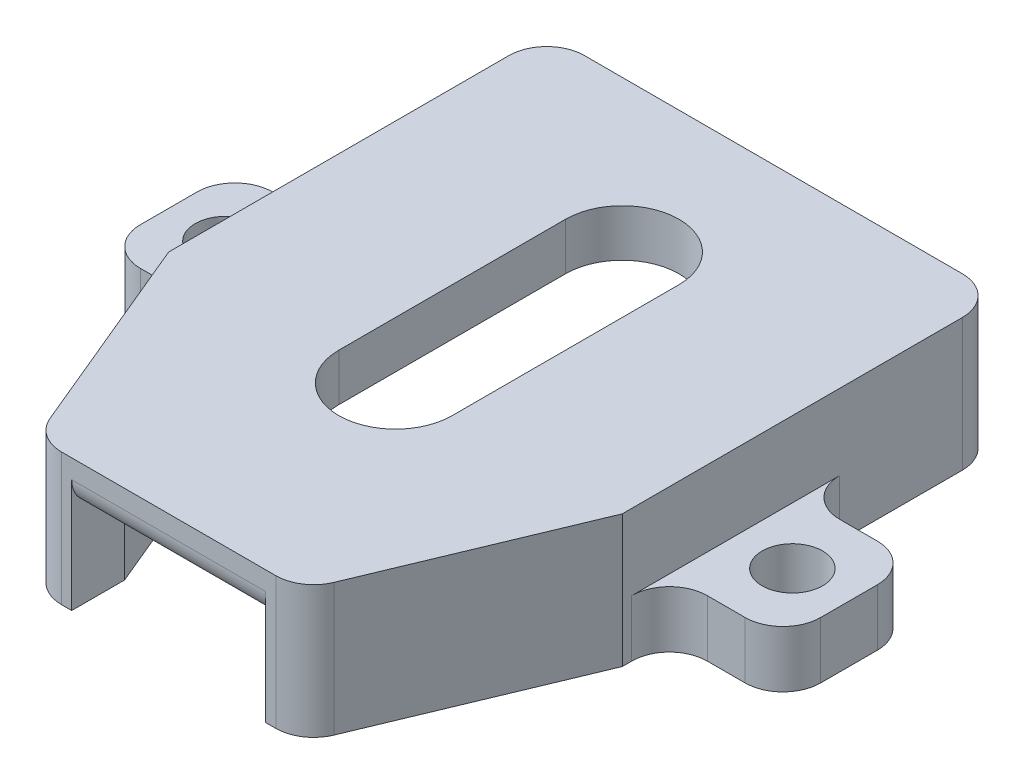
SolidWorks part; units mm, degrees
ref_plane "前视基准面" through (0, 0, 0) normal (0, 0, 1) x (1, 0, 0)
ref_plane "上视基准面" through (0, 0, 0) normal (0, 1, 0) x (1, 0, 0)
ref_plane "右视基准面" through (0, 0, 0) normal (1, 0, 0) x (0, 0, -1)
sketch "草图1" plane through (0, 0, 0) normal (0, 0, 1) x (1, 0, 0)
  line L0 (0, 148.5) -> (0, -94.9538) construction
  line L1 (105, -148.5) -> (-105, -148.5) construction
  line L2 (105, -148.5) -> (105, 148.5) construction
  line L3 (105, 148.5) -> (-105, 148.5) construction
  line L4 (-105, -148.5) -> (-105, 148.5) construction
  line L5 (105, -148.5) -> (-105, 148.5) construction
  line L6 (105, 148.5) -> (-105, -148.5) construction
  line L7 (35.8892, 121.6645) -> (-35.8892, 121.6645)
  line L8 (-35.8892, 121.6645) -> (-66.9017, 102.292)
  line L9 (-75, 40.9339) -> (-75, 31.2613)
  line L10 (-66.9017, 102.292) -> (-66.9017, 52.8701)
  line L11 (75, 40.9339) -> (75, 31.2613)
  line L12 (66.9017, 102.292) -> (66.9017, 52.8701)
  line L13 (35.8892, 121.6645) -> (66.9017, 102.292)
  line L14 (-75, 31.2613) -> (75, 31.2613)
  line L15 (-60, -148.5) -> (-60, -91.8129)
  line L16 (-75, 23.94) -> (75, 23.94)
  line L17 (-75, 23.94) -> (-75, 10.5626)
  line L18 (-38.8455, -105.5906) -> (-66.4608, -113.7617)
  line L19 (-66.4608, -113.7617) -> (-70.1743, -102.7328)
  line L20 (75, 23.94) -> (75, 10.5626)
  line L21 (66.4608, -113.7617) -> (70.1743, -102.7328)
  line L22 (38.8455, -105.5906) -> (66.4608, -113.7617)
  line L23 (-105, 93.0519) -> (105, 93.0519)
  line L24 (-105, 63.0519) -> (105, 63.0519)
  line L25 (-105, -90.0629) -> (-70.5337, -90.0629)
  line L26 (-105, -60.0629) -> (-67.4027, -60.0629)
  line L27 (60, -148.5) -> (60, 148.5)
  line L28 (-60, -58.3129) -> (-45, -58.3129)
  line L29 (-60, -61.8129) -> (-45, -61.8129)
  line L30 (-36, -58.3129) -> (-21, -58.3129)
  line L31 (-36, -61.8129) -> (-21, -61.8129)
  line L32 (-60, -88.3129) -> (-45, -88.3129)
  line L33 (-60, -91.8129) -> (-45, -91.8129)
  line L34 (-36, -88.3129) -> (-21, -88.3129)
  line L35 (-36, -91.8129) -> (-21, -91.8129)
  line L36 (-60, -58.3129) -> (-60, 148.5)
  line L37 (-19.25, -90.0629) -> (105, -90.0629)
  line L38 (-19.25, -60.0629) -> (19.25, -60.0629)
  line L39 (-60, -88.3129) -> (-60, -61.8129)
  line L40 (21, -58.3129) -> (36, -58.3129)
  line L41 (45, -58.3129) -> (60, -58.3129)
  line L42 (60, -61.8129) -> (45, -61.8129)
  line L43 (36, -61.8129) -> (21, -61.8129)
  line L44 (21, -88.3129) -> (36, -88.3129)
  line L45 (21, -91.8129) -> (36, -91.8129)
  line L46 (45, -88.3129) -> (60, -88.3129)
  line L47 (45, -91.8129) -> (60, -91.8129)
  line L48 (37.75, -60.0629) -> (43.25, -60.0629)
  line L49 (58.25, -60.0629) -> (105, -60.0629)
  line L50 (-60, 94.8019) -> (-45, 94.8019)
  line L51 (-36, 94.8019) -> (-21, 94.8019)
  line L52 (-60, 91.3019) -> (-45, 91.3019)
  line L53 (-36, 91.3019) -> (-21, 91.3019)
  line L54 (-60, 64.8019) -> (-45, 64.8019)
  line L55 (-60, 61.3019) -> (-45, 61.3019)
  line L56 (-36, 64.8019) -> (-21, 64.8019)
  line L57 (-36, 61.3019) -> (-21, 61.3019)
  line L58 (21, 94.8019) -> (36, 94.8019)
  line L59 (21, 91.3019) -> (36, 91.3019)
  line L60 (45, 94.8019) -> (60, 94.8019)
  line L61 (45, 91.3019) -> (60, 91.3019)
  line L62 (21, 61.3019) -> (36, 61.3019)
  line L63 (21, 64.8019) -> (36, 64.8019)
  line L64 (45, 61.3019) -> (60, 61.3019)
  line L65 (45, 64.8019) -> (60, 64.8019)
  line L66 (-33.1709, -104.7687) -> (33.1709, -104.7687)
  line L67 (0, -104.7687) -> (0, -148.5) construction
  arc A0 (-75, 40.9339) -> (-66.9017, 52.8701) centre (-79.7474, 52.8701) ccw
  arc A1 (75, 40.9339) -> (66.9017, 52.8701) centre (79.7474, 52.8701) cw
  arc A3 (-60, -88.3129) -> (-60, -91.8129) centre (-60, -90.0629) ccw
  arc A4 (-60, -58.3129) -> (-60, -61.8129) centre (-60, -60.0629) ccw
  circle A5 centre (-60, 63.0519) radius 1.75
  circle A6 centre (-60, 93.0519) radius 1.75
  circle A7 centre (60, 93.0519) radius 1.75
  circle A8 centre (60, 63.0519) radius 1.75
  arc A9 (60, -91.8129) -> (60, -88.3129) centre (60, -90.0629) ccw
  arc A10 (60, -61.8129) -> (60, -58.3129) centre (60, -60.0629) ccw
  arc A11 (-36, -58.3129) -> (-36, -61.8129) centre (-36, -60.0629) ccw
  arc A12 (-36, -88.3129) -> (-36, -91.8129) centre (-36, -90.0629) ccw
  arc A13 (36, -61.8129) -> (36, -58.3129) centre (36, -60.0629) ccw
  arc A14 (36, -91.8129) -> (36, -88.3129) centre (36, -90.0629) ccw
  arc A15 (-45, -61.8129) -> (-45, -58.3129) centre (-45, -60.0629) ccw
  arc A16 (-21, -61.8129) -> (-21, -58.3129) centre (-21, -60.0629) ccw
  arc A17 (-45, -91.8129) -> (-45, -88.3129) centre (-45, -90.0629) ccw
  arc A18 (-21, -91.8129) -> (-21, -88.3129) centre (-21, -90.0629) ccw
  arc A19 (45, -58.3129) -> (45, -61.8129) centre (45, -60.0629) ccw
  arc A20 (21, -58.3129) -> (21, -61.8129) centre (21, -60.0629) ccw
  arc A21 (21, -88.3129) -> (21, -91.8129) centre (21, -90.0629) ccw
  arc A22 (45, -88.3129) -> (45, -91.8129) centre (45, -90.0629) ccw
  circle A23 centre (-36, 93.0519) radius 1.75
  circle A24 centre (-36, 63.0519) radius 1.75
  circle A25 centre (36, 93.0519) radius 1.75
  circle A26 centre (36, 63.0519) radius 1.75
  circle A27 centre (-45, 93.0519) radius 1.75
  circle A28 centre (-21, 93.0519) radius 1.75
  circle A29 centre (-45, 63.0519) radius 1.75
  circle A30 centre (-21, 63.0519) radius 1.75
  circle A31 centre (21, 93.0519) radius 1.75
  circle A32 centre (21, 63.0519) radius 1.75
  circle A33 centre (45, 93.0519) radius 1.75
  circle A34 centre (45, 63.0519) radius 1.75
  arc A35 (33.1709, -104.7687) -> (38.8455, -105.5906) centre (33.1709, -124.7687) cw
  arc A36 (-33.1709, -104.7687) -> (-38.8455, -105.5906) centre (-33.1709, -124.7687) ccw
  spline S0 degree 3 poles (-75, 10.5626) (-72.6959, 1.9073) (-70.3396, -13.3728) (-67.1028, -43.6255) (-66.7657, -72.9327) (-71.8903, -95.1489) (-70.1743, -102.7328) knots 0 0 0 0 0.235247 0.406294 0.801186 1 1 1 1
  spline S1 degree 3 poles (75, 10.5626) (72.6959, 1.9073) (70.3396, -13.3728) (67.1028, -43.6255) (66.7657, -72.9327) (71.8903, -95.1489) (70.1743, -102.7328) knots 0 0 0 0 0.235247 0.406294 0.801186 1 1 1 1
  point P0 (0, 0)
  point P27 (0, 121.6645)
  point P42 (0, -94.0966)
  dimension "D1" = 60
  dimension "D4" = 20
  dimension "D5" = 24
  dimension "D7" = 24
  dimension "D9" = 15
  dimension "D10" = 15
  dimension "D13" = 24
  dimension "D17" = 15
  dimension "D2" = 30
  dimension "D3" = 30
  dimension "D6" = 24
  dimension "D8" = 24
  dimension "D11" = 15
  dimension "D12" = 15
  dimension "D14" = 24
  dimension "D15" = 24
  dimension "D16" = 24
  dimension "D18" = 15
  dimension "D19" = 15
  dimension "D20" = 15
  dimension "D21" = 15
  dimension "D22" = 15
  dimension "D23" = 15
  dimension "D24" = 15
  dimension "D25" = 15
  dimension "D26" = 15
  dimension "D27" = 15
  dimension "D28" = 15
  dimension "D29" = 3.5
  dimension "D30" = 3.5
  dimension "D31" = 3.5
extrude "凸台-拉伸1" add sketch "草图1" along normal blind 3 contours A34 L24 A26 L62 A32 A30 L57 A24 A29 L55 L36 L14 L27 L64 | A5 L24 L10 A0 L9 L14 L36 | A6 L23 L10 L24 A5 L36 | A6 L36 L8 L10 L23 | A33 L60 L27 L13 L7 L8 L36 L50 A27 L23 A23 L51 A28 A31 L58 A25 | A34 L65 L27 L61 A33 L23 A25 L59 A31 A28 L53 A23 A27 L52 L36 L54 A29 L24 A24 L56 A30 A32 L63 A26 | A7 L23 L12 L13 L27 | A8 L24 L12 L23 A7 L27 | A8 L27 L14 L11 A1 L12 L24 | A22 L46 L27 L42 A19 A13 L43 A20 A16 L31 A11 L30 L40 L41 L16 L36 L28 A15 L29 L39 L32 A17 L33 L15 L18 L22 L47 A14 L45 A21 A18 L35 A12 L34 | L17 S0 L19 L18 L15 A3 L39 A4 L36 L16 | S1 L20 L16 L27 A10 L49 | S1 L49 A10 L27 A9 L37 | S1 L37 A9 L27 L22 L21 region at (0, 106.7597, 0) region at (63.3118, 98.9762, 0) region at (-63.3118, 98.9762, 0) region at (63.5153, 78.0519, 0) region at (-63.5153, 78.0519, 0) region at (65.7633, 44.067, 0) region at (0, 78.0519, 0) region at (-65.7633, 44.067, 0) region at (0, 46.6707, 0) region at (0, -40.0712, 0) region at (65.6849, -11.6712, 0) region at (-65.3451, -38.0027, 0) region at (64.4303, -76.0355, 0) region at (65.0264, -100.7629, 0)
sketch "草图7" plane through (0, 0, 0) normal (0, 0, -1) x (-1, 0, 0)
  line L0 (0, 121.6645) -> (0, -104.7687) construction
  line L1 (-35.8892, 121.6645) -> (35.8892, 121.6645) construction
  line L2 (33.1709, -104.7687) -> (-33.1709, -104.7687) construction
  line L3 (0, 41.2613) -> (-21, 41.2613) construction
  line L4 (0, 41.2613) -> (21, 41.2613) construction
  line L5 (0, 13.94) -> (-21, 13.94) construction
  line L6 (0, 13.94) -> (21, 13.94) construction
  line L7 (75, 23.94) -> (-75, 23.94) construction
  line L8 (75, 31.2613) -> (-75, 31.2613) construction
  circle A0 centre (-21, 41.2613) radius 1.75
  circle A1 centre (21, 41.2613) radius 1.75
  circle A2 centre (-21, 13.94) radius 2.25
  circle A3 centre (21, 13.94) radius 2.25
  dimension "D1" = 10
  dimension "D2" = 10
extrude "切除-拉伸2" cut sketch "草图7" against normal through all
sketch "草图9" plane through (0, 0, 3) normal (0, 0, 1) x (1, 0, 0)
  line L0 (-70.7828, -98.747) -> (70.7828, -98.747) construction
  line L1 (0, -98.747) -> (0, -104.7687) construction
  line L2 (55, -100.497) -> (20, -100.497)
  line L3 (-55, -96.997) -> (-20, -96.997)
  line L4 (-55, -100.497) -> (-20, -100.497)
  line L5 (-33.1709, -104.7687) -> (33.1709, -104.7687) construction
  line L6 (55, -96.997) -> (20, -96.997)
  arc A0 (-55, -96.997) -> (-55, -100.497) centre (-55, -98.747) ccw
  arc A1 (-20, -100.497) -> (-20, -96.997) centre (-20, -98.747) ccw
  arc A2 (20, -100.497) -> (20, -96.997) centre (20, -98.747) cw
  arc A3 (55, -96.997) -> (55, -100.497) centre (55, -98.747) cw
  spline S0 degree 3 poles (-75, 10.5626) (-72.6959, 1.9073) (-70.3396, -13.3728) (-67.1028, -43.6255) (-66.7657, -72.9327) (-71.8903, -95.1489) (-70.1743, -102.7328) knots 0 0 0 0 0.235247 0.406294 0.801186 1 1 1 1 construction
  spline S1 degree 3 poles (75, 10.5626) (72.6959, 1.9073) (70.3396, -13.3728) (67.1028, -43.6255) (66.7657, -72.9327) (71.8903, -95.1489) (70.1743, -102.7328) knots 0 0 0 0 0.235247 0.406294 0.801186 1 1 1 1 construction
  dimension "D1" = 35
  dimension "D2" = 20
extrude "切除-拉伸4" cut sketch "草图9" against normal blind 3
sketch "草图10" plane through (0, 0, 3) normal (0, 0, 1) x (1, 0, 0)
  line L0 (-21, -60.0629) -> (-21, -90.0629) construction
  line L1 (21, -60.0629) -> (21, -90.0629) construction
  line L2 (-21, -75.0629) -> (-17.5, -75.0629) construction
  line L4 (12.5, -80.0629) -> (-12.5, -80.0629)
  line L6 (12.5, -70.0629) -> (-12.5, -70.0629)
  line L11 (17.5, -75.0629) -> (21, -75.0629) construction
  arc A0 (-12.5, -70.0629) -> (-12.5, -80.0629) centre (-12.5, -75.0629) ccw
  arc A1 (12.5, -80.0629) -> (12.5, -70.0629) centre (12.5, -75.0629) ccw
  point P11 (0, -75.0629)
extrude "切除-拉伸5" cut sketch "草图10" against normal blind 3
sketch "草图11" plane through (0, 0, 3) normal (0, 0, 1) x (1, 0, 0)
  line L0 (-21, 93.0519) -> (-21, 63.0519) construction
  line L1 (21, 93.0519) -> (21, 63.0519) construction
  line L2 (-21, 78.0519) -> (-20, 78.0519) construction
  line L4 (15, 73.0519) -> (-15, 73.0519)
  line L6 (15, 83.0519) -> (-15, 83.0519)
  line L10 (20, 78.0519) -> (21, 78.0519) construction
  arc A0 (-15, 83.0519) -> (-15, 73.0519) centre (-15, 78.0519) ccw
  arc A1 (15, 73.0519) -> (15, 83.0519) centre (15, 78.0519) ccw
  point P10 (0, 78.0519)
  dimension "D1" = 30
extrude "切除-拉伸8" cut sketch "草图11" against normal blind 3
sketch "草图12" plane through (0, 0, 3) normal (0, 0, 1) x (1, 0, 0)
  line L0 (0, 121.6645) -> (0, 83.0519) construction
  line L1 (35.8892, 121.6645) -> (-35.8892, 121.6645) construction
  line L2 (15, 83.0519) -> (-15, 83.0519) construction
  circle A0 centre (0, 106.3718) radius 11 construction
  circle A1 centre (0, 106.3718) radius 8 construction
  circle A2 centre (0, 114.3718) radius 1.7
  circle A3 centre (0, 98.3718) radius 1.7
  circle A4 centre (8, 106.3718) radius 1.7
  circle A5 centre (-8, 106.3718) radius 1.7
extrude "切除-拉伸9" cut sketch "草图12" against normal blind 3
sketch "草图13" plane through (0, 0, 3) normal (0, 0, 1) x (1, 0, 0)
  line L0 (0, -104.7687) -> (0, -80.0629) construction
  line L1 (-33.1709, -104.7687) -> (33.1709, -104.7687) construction
  line L2 (-12.5, -80.0629) -> (12.5, -80.0629) construction
  circle A0 centre (0, -92.4158) radius 8 construction
  circle A1 centre (0, -84.4158) radius 1.7
  circle A2 centre (8, -92.4158) radius 1.7
  circle A3 centre (0, -100.4158) radius 1.7
  circle A4 centre (-8, -92.4158) radius 1.7
extrude "切除-拉伸11" cut sketch "草图13" against normal blind 3
sketch "草图14" plane through (0, 0, 3) normal (0, 0, 1) x (1, 0, 0)
  line L0 (0, 23.94) -> (0, -104.7687) construction
  line L1 (-55.4755, 8.9197) -> (-55.4755, -46.0803)
  line L2 (-58.9755, 8.9197) -> (-58.9755, -46.0803)
  line L3 (-75, 23.94) -> (75, 23.94) construction
  line L4 (-33.1709, -104.7687) -> (33.1709, -104.7687) construction
  line L5 (58.9755, 8.9197) -> (58.9755, -46.0803)
  line L6 (55.4755, 8.9197) -> (55.4755, -46.0803)
  arc A0 (-55.4755, 8.9197) -> (-58.9755, 8.9197) centre (-57.2255, 8.9197) ccw
  arc A1 (-58.9755, -46.0803) -> (-55.4755, -46.0803) centre (-57.2255, -46.0803) ccw
  arc A2 (58.9755, -46.0803) -> (55.4755, -46.0803) centre (57.2255, -46.0803) cw
  arc A3 (55.4755, 8.9197) -> (58.9755, 8.9197) centre (57.2255, 8.9197) cw
extrude "切除-拉伸12" cut sketch "草图14" against normal through all
fillet "圆角1" radius 2 2 edges at (75, 31.2613, 1.5) (-75, 31.2613, 1.5)
fillet "圆角2" radius 2 2 edges at (-75, 23.94, 1.5) (75, 23.94, 1.5)
sketch "草图15" plane through (0, 0, 0) normal (0, 0, -1) x (-1, 0, 0)
  line L0 (0, 121.6645) -> (0, 31.2613) construction
  line L1 (-35.8892, 121.6645) -> (35.8892, 121.6645) construction
  line L2 (73, 31.2613) -> (-73, 31.2613) construction
  line L3 (-27.5188, 121.6645) -> (-63.6963, 99.0657) construction
  line L4 (-35.8892, 121.6645) -> (-66.9017, 102.292) construction
  line L5 (-61.1842, 102.4035) -> (-34.7748, 118.9006)
  line L6 (-59.5948, 99.8591) -> (-33.1854, 116.3562)
  line L7 (27.5188, 121.6645) -> (63.6963, 99.0657) construction
  line L8 (59.5948, 99.8591) -> (33.1854, 116.3562)
  line L9 (61.1842, 102.4035) -> (34.7748, 118.9006)
  arc A0 (-61.1842, 102.4035) -> (-59.5948, 99.8591) centre (-60.3895, 101.1313) ccw
  arc A1 (-33.1854, 116.3562) -> (-34.7748, 118.9006) centre (-33.9801, 117.6284) ccw
  arc A2 (33.1854, 116.3562) -> (34.7748, 118.9006) centre (33.9801, 117.6284) cw
  arc A3 (61.1842, 102.4035) -> (59.5948, 99.8591) centre (60.3895, 101.1313) cw
extrude "切除-拉伸13" cut sketch "草图15" against normal through all
sketch "草图16" plane through (0, 0, 0) normal (0, 0, -1) x (-1, 0, 0)
  line L0 (0, 121.6645) -> (0, 31.2613) construction
  line L1 (-35.8892, 121.6645) -> (35.8892, 121.6645) construction
  line L2 (73, 31.2613) -> (-73, 31.2613) construction
  line L3 (-21, 41.2613) -> (-66.71, 41.2613) construction
  line L4 (-62, 43.0113) -> (-32, 43.0113)
  line L5 (-62, 39.5113) -> (-32, 39.5113)
  line L6 (21, 41.2613) -> (66.71, 41.2613) construction
  line L7 (62, 39.5113) -> (32, 39.5113)
  line L8 (62, 43.0113) -> (32, 43.0113)
  line L9 (-75, 40.9339) -> (-75, 33.2613) construction
  arc A0 (-62, 43.0113) -> (-62, 39.5113) centre (-62, 41.2613) ccw
  arc A1 (-32, 39.5113) -> (-32, 43.0113) centre (-32, 41.2613) ccw
  arc A2 (32, 39.5113) -> (32, 43.0113) centre (32, 41.2613) cw
  arc A3 (62, 43.0113) -> (62, 39.5113) centre (62, 41.2613) cw
  dimension "D2" = 13
sketch "草图17" plane through (0, 0, 0) normal (0, 0, -1) x (-1, 0, 0)
  text T0 "Y" font "黑体" height in points 72
extrude "切除-拉伸15" cut sketch "草图17" against normal through all
sketch "草图18" plane through (0, 0, 0) normal (0, 0, -1) x (-1, 0, 0)
  text T0 "H" font "黑体" height in points 72
extrude "切除-拉伸16" cut sketch "草图18" against normal through all
sketch "草图20" plane through (0, 0, 0) normal (0, 0, -1) x (-1, 0, 0)
  line L0 (-66.9017, 102.292) -> (-66.9017, 52.8701) construction
  line L1 (-66.9017, 95.8596) -> (66.9017, 95.8596)
  line L2 (-66.9017, 95.8596) -> (-66.9017, 52.8701)
  line L3 (-66.9017, 52.8701) -> (66.9017, 52.8701)
  line L4 (66.9017, 95.8596) -> (66.9017, 52.8701)
extrude "凸台-拉伸2" add sketch "草图20" against normal blind 3
sketch "草图21" plane through (0, 0, 0) normal (0, 0, -1) x (-1, 0, 0)
  line L1 (-64.7663, -56.4228) -> (64.4409, -56.4228)
  line L2 (-64.7663, -56.4228) -> (-64.7663, -95.2117)
  line L3 (-64.7663, -95.2117) -> (64.4409, -95.2117)
  line L4 (64.4409, -56.4228) -> (64.4409, -95.2117)
extrude "凸台-拉伸3" add sketch "草图21" against normal blind 3
sketch "草图22" plane through (0, 0, 0) normal (0, 0, -1) x (-1, 0, 0)
  line L1 (-46.7188, -3.1128) -> (-25.8503, -3.1128)
  line L2 (-46.7188, -3.1128) -> (-46.7188, -34.3233)
  line L3 (-46.7188, -34.3233) -> (-25.8503, -34.3233)
  line L4 (-25.8503, -3.1128) -> (-25.8503, -34.3233)
  line L5 (28.8143, -3.1128) -> (49.8675, -3.1128)
  line L6 (28.8143, -3.1128) -> (28.8143, -33.2152)
  line L7 (28.8143, -33.2152) -> (49.8675, -33.2152)
  line L8 (49.8675, -3.1128) -> (49.8675, -33.2152)
extrude "凸台-拉伸4" add sketch "草图22" against normal blind 3
sketch "草图24" plane through (0, 0, 0) normal (0, 0, -1) x (-1, 0, 0)
  line L1 (-64.9961, 44.3276) -> (-28.6954, 44.3276)
  line L2 (-64.9961, 44.3276) -> (-64.9961, 38.3743)
  line L3 (-64.9961, 38.3743) -> (-28.6954, 38.3743)
  line L4 (-28.6954, 44.3276) -> (-28.6954, 38.3743)
  line L5 (29.2405, 44.3276) -> (65.8315, 44.3276)
  line L6 (29.2405, 44.3276) -> (29.2405, 38.3743)
  line L7 (29.2405, 38.3743) -> (65.8315, 38.3743)
  line L8 (65.8315, 44.3276) -> (65.8315, 38.3743)
extrude "凸台-拉伸5" add sketch "草图24" against normal blind 3
sketch "草图25" plane through (0, 0, 0) normal (0, 0, -1) x (-1, 0, 0)
  line L0 (-32.6582, 113.0113) -> (-14.6582, 113.0113)
  line L1 (-32.6582, 109.5113) -> (-14.6582, 109.5113)
  line L2 (-21, 41.2613) -> (21, 41.2613)
  line L3 (-0.3165, 111.2613) -> (0, 41.2613) construction
  line L4 (14.3418, 113.0113) -> (32.3418, 113.0113)
  line L5 (32.3418, 41.2613) -> (-32.6582, 41.2613)
  line L6 (32.3418, 41.2613) -> (32.3418, 111.2613)
  line L8 (-32.6582, 41.2613) -> (-32.6582, 111.2613)
  line L9 (32.3418, 41.2613) -> (-32.6582, 111.2613) construction
  line L10 (30.7168, 109.5113) -> (-32.6582, 41.2613) construction
  line L11 (14.3418, 109.5113) -> (32.3418, 109.5113)
  line L12 (32.3418, 76.2613) -> (-32.6582, 76.2613) construction
  line L13 (12.5918, 111.2613) -> (-12.9082, 111.2613)
  line L14 (12.5918, 41.2613) -> (-12.9082, 41.2613)
  line L15 (14.3418, 43.0113) -> (32.3418, 43.0113)
  line L16 (14.3418, 39.5113) -> (32.3418, 39.5113)
  line L17 (-32.6582, 43.0113) -> (-14.6582, 43.0113)
  line L18 (-32.6582, 39.5113) -> (-14.6582, 39.5113)
  circle A0 centre (-32.6582, 111.2613) radius 1.75
  arc A1 (32.3418, 109.5113) -> (32.3418, 113.0113) centre (32.3418, 111.2613) ccw
  arc A2 (-14.6582, 109.5113) -> (-14.6582, 113.0113) centre (-14.6582, 111.2613) ccw
  arc A3 (14.3418, 113.0113) -> (14.3418, 109.5113) centre (14.3418, 111.2613) ccw
  arc A4 (14.3418, 39.5113) -> (14.3418, 43.0113) centre (14.3418, 41.2613) cw
  arc A5 (-14.6582, 43.0113) -> (-14.6582, 39.5113) centre (-14.6582, 41.2613) cw
  arc A6 (32.3418, 43.0113) -> (32.3418, 39.5113) centre (32.3418, 41.2613) cw
  circle A7 centre (-32.6582, 41.2613) radius 1.75
  point P9 (-0.1582, 76.2613)
  circle M6 centre (-21, 41.2613) radius 1.75
  circle M7 centre (21, 41.2613) radius 1.75
  dimension "D1" = 18
  dimension "D2" = 18
extrude "切除-拉伸17" cut sketch "草图25" against normal through all contours A0 | A2 L0 A0 L1 | L4 A3 L11 A1 | A7 L8 L5 | A7 L5 L8 | L17 A7 L5 M6 | L5 A7 L18 M6 | A5 L17 L2 M6 | A5 L2 L18 M6 | L17 L5 L2 M6 | L18 L2 L5 M6 | A4 L2 L15 M7 | A4 L16 L2 M7 | L16 L5 L2 M7 | L15 L2 L5 M7 | L15 L5 L6 M7 | A6 L6 L5 L16 M7 region at (22.2838, 111.2613, 0) region at (31.4558, 112.4638, 0) region at (31.9155, 42.0041, 0) region at (26.8291, 42.1772, 0) region at (32.9058, 41.0138, 0) region at (-23.3418, 111.2613, 0) region at (16.4547, 42.1363, 0) region at (21, 42.0041, 0) region at (26.8291, 40.3455, 0) region at (21, 40.5186, 0) region at (16.4547, 40.3863, 0) region at (-28.59, 40.5612, 0) region at (-27.3505, 42.1546, 0) region at (-16.2964, 42.1363, 0) region at (-16.2964, 40.3863, 0) region at (-21, 42.0041, 0) region at (-21, 40.5186, 0)
extrude "切除-拉伸19" cut sketch "草图16" against normal through all
sketch "草图26" plane through (0, 0, 0) normal (0, 0, -1) x (-1, 0, 0)
  line L0 (0, 121.6645) -> (0, -104.7687) construction
  line L1 (-35.8892, 121.6645) -> (35.8892, 121.6645) construction
  line L2 (33.1709, -104.7687) -> (-33.1709, -104.7687) construction
  line L4 (15, 71.877) -> (-15, 71.877)
  line L6 (15, 81.877) -> (-15, 81.877)
  arc A0 (-15, 81.877) -> (-15, 71.877) centre (-15, 76.877) ccw
  arc A1 (15, 71.877) -> (15, 81.877) centre (15, 76.877) ccw
  point P6 (0, 76.877)
extrude "切除-拉伸20" cut sketch "草图26" against normal through all
sketch "草图27" plane through (0, 0, 0) normal (0, 0, -1) x (-1, 0, 0)
  line L0 (0, 23.94) -> (0, -104.7687) construction
  line L1 (73, 23.94) -> (-73, 23.94) construction
  line L2 (33.1709, -104.7687) -> (-33.1709, -104.7687) construction
  line L3 (-42.5, -15.81) -> (-10, -15.81)
  line L4 (42.5, -17.56) -> (-42.5, -17.56)
  line L5 (42.5, -17.56) -> (42.5, 5.44)
  line L6 (42.5, 5.44) -> (-42.5, 5.44)
  line L7 (-42.5, -17.56) -> (-42.5, 5.44)
  line L8 (42.5, -17.56) -> (-42.5, 5.44) construction
  line L9 (42.5, 5.44) -> (-42.5, -17.56) construction
  line L10 (-42.5, -19.31) -> (-10, -19.31)
  line L11 (-42.5, 7.19) -> (-10, 7.19)
  line L12 (-42.5, 3.69) -> (-10, 3.69)
  line L13 (10, 7.19) -> (42.5, 7.19)
  line L14 (10, 3.69) -> (42.5, 3.69)
  line L15 (10, -15.81) -> (42.5, -15.81)
  line L16 (10, -19.31) -> (42.5, -19.31)
  circle A0 centre (-42.5, 5.44) radius 1.75
  circle A1 centre (-42.5, -17.56) radius 1.75
  circle A2 centre (42.5, 5.44) radius 1.75
  circle A3 centre (42.5, -17.56) radius 1.75
  circle A4 centre (-10, 5.44) radius 1.75
  circle A5 centre (-10, -17.56) radius 1.75
  circle A6 centre (10, -17.56) radius 1.75
  circle A7 centre (10, 5.44) radius 1.75
  point P6 (0, -6.06)
  dimension "D4" = 10
  dimension "D5" = 10
  dimension "D1" = 30
  dimension "D2" = 85
  dimension "D3" = 23
extrude "切除-拉伸21" cut sketch "草图27" against normal through all contours L6 A0 L7 | L7 A0 L6 | A4 L11 A0 L6 | A4 L6 A0 L12 | L6 A4 | L6 A4 | A7 L6 | A7 L6 | L6 A7 L14 A2 | L13 A7 L6 A2 | A2 L6 L5 | L6 A2 L5 | L7 A1 L4 | L4 A1 L7 | A5 L3 A1 L4 | A5 L4 A1 L10 | L4 A5 | L4 A5 | A6 L4 | A6 L4 | L4 A6 L16 A3 | L15 A6 L4 A3 | L4 A3 L5 | L5 A3 L4 region at (41.7573, -16.8172, 0) region at (26.25, -16.6727, 0) region at (42.7476, -17.8075, 0) region at (10, -16.8172, 0) region at (42.7476, 5.6876, 0) region at (26.25, 4.5528, 0) region at (41.7573, 4.6973, 0) region at (26.25, -18.4472, 0) region at (10, -18.3027, 0) region at (10, 4.6973, 0) region at (26.25, 6.3273, 0) region at (-10, -16.8172, 0) region at (-10, -18.3027, 0) region at (10, 6.1828, 0) region at (-26.25, -16.6727, 0) region at (-26.25, -18.4472, 0) region at (-10, 6.1828, 0) region at (-10, 4.6973, 0) region at (-41.7573, -16.8172, 0) region at (-42.7476, -17.8075, 0) region at (-26.25, 6.3273, 0) region at (-26.25, 4.5528, 0) region at (-41.7573, 4.6973, 0) region at (-42.7476, 5.6876, 0)
sketch "草图28" plane through (0, 0, 0) normal (0, 0, -1) x (-1, 0, 0)
  line L0 (0, 23.94) -> (0, -104.7687) construction
  line L1 (73, 23.94) -> (-73, 23.94) construction
  line L2 (33.1709, -104.7687) -> (-33.1709, -104.7687) construction
  arc A0 (0, -48.8123) -> (-10.2848, -54.2659) centre (-5.1424, -51.5391) ccw
  arc A1 (-10.2848, -54.2659) -> (0, -63.7557) centre (7.9187, -44.8556) ccw
  arc A2 (10.2848, -54.2659) -> (0, -63.7557) centre (-7.9187, -44.8556) cw
  arc A3 (0, -48.8123) -> (10.2848, -54.2659) centre (5.1424, -51.5391) cw
extrude "切除-拉伸22" cut sketch "草图28" against normal through all
sketch "草图29" plane through (0, 0, 0) normal (0, 0, -1) x (-1, 0, 0)
  line L0 (0, 23.94) -> (0, -104.7687) construction
  line L1 (73, 23.94) -> (-73, 23.94) construction
  line L2 (33.1709, -104.7687) -> (-33.1709, -104.7687) construction
  arc A0 (-21.3687, -73.4908) -> (21.3687, -73.4908) centre (0, -58.7579) ccw
  arc A1 (-24.1996, -75.4426) -> (24.1996, -75.4426) centre (0, -58.7579) ccw
  arc A2 (-21.3687, -73.4908) -> (-24.1996, -75.4426) centre (-22.7842, -74.4667) ccw
  arc A3 (24.1996, -75.4426) -> (21.3687, -73.4908) centre (22.7842, -74.4667) ccw
extrude "切除-拉伸23" cut sketch "草图29" against normal blind 3
ref_plane "基准面1" through (0, 0, -10) normal (0, 0, -1) x (-1, 0, 0)
sketch "草图30" plane through (0, 0, -10) normal (0, 0, -1) x (-1, 0, 0)
  line L0 (-8, 106.3718) -> (8, 106.3718) construction
  line L1 (-12, 106.3718) -> (-12, 141.6645)
  line L2 (12, 106.3718) -> (12, 141.6645)
  line L3 (-35.8892, 121.6645) -> (35.8892, 121.6645) construction
  line L4 (-12, 141.6645) -> (12, 141.6645)
  circle A0 centre (8, 106.3718) radius 1.7 construction
  circle A1 centre (0, 98.3718) radius 1.7 construction
  circle A2 centre (-8, 106.3718) radius 1.7 construction
  circle A3 centre (0, 114.3718) radius 1.7 construction
  circle A4 centre (8, 106.3718) radius 1.7
  circle A5 centre (0, 98.3718) radius 1.7
  circle A6 centre (-8, 106.3718) radius 1.7
  circle A7 centre (0, 114.3718) radius 1.7
  arc A8 (-12, 106.3718) -> (12, 106.3718) centre (0, 106.3718) ccw
  circle A9 centre (0, 106.3718) radius 3.5
  dimension "D1" = 20
  dimension "D2" = 20
extrude "凸台-拉伸6" add sketch "草图30" along normal blind 4 separate body
sketch "草图31" plane through (-12, 0, 0) normal (-1, 0, 0) x (0, 0, 1)
  line L0 (0, 121.6645) -> (-10, 121.6645) construction
  line L2 (-10, 121.6645) -> (-10, 125.8643) construction
  line L4 (-10, 121.6645) -> (15, 129.6645)
  line L5 (-10, 125.8643) -> (15, 133.8643)
  line L6 (15, 133.8643) -> (15, 139.3643)
  line L7 (18, 130.6245) -> (18, 139.3643)
  line L8 (15, 129.6645) -> (18, 130.6245)
  line L9 (15, 139.3643) -> (18, 139.3643)
  line L10 (-10, 121.6645) -> (-10, 125.8643)
  dimension "D1" = 25
  dimension "D2" = 5.5
  dimension "D3" = 4
  dimension "D4" = 3
extrude "凸台-拉伸7" add sketch "草图31" against normal up to surface (24 mm away) up to face at (12, 124.0182, -12)
sketch "草图32" plane through (-12, 0, 0) normal (-1, 0, 0) x (0, 0, 1)
  line L0 (15, 133.8643) -> (-10, 125.8643) construction
  line L1 (15, 133.8643) -> (-10, 125.8643)
  line L2 (-10, 125.8643) -> (-14, 124.5843)
  line L5 (-10, 141.6645) -> (-10, 125.8643)
  line L6 (-14, 106.3718) -> (-14, 141.6645) construction
  line L7 (-14, 141.6645) -> (-10, 141.6645) construction
  line L8 (-14, 141.6645) -> (-10, 141.6645)
  line L9 (-14, 106.3718) -> (-14, 141.6645)
  line M12 (-10, 125.8643) -> (-10, 141.6645)
  line M13 (-10, 141.6645) -> (-14, 141.6645)
  line M14 (-14, 141.6645) -> (-14, 106.3718)
extrude "切除-拉伸26" cut sketch "草图32" against normal blind 31.5 contours L2 M12 M13 M14 region at (-12, 133.4403, -12.026)
sketch "草图34" plane through (0, 139.3643, 0) normal (0, 1, 0) x (1, 0, 0)
  line L0 (0, -18.0398) -> (0, 14) construction
  line L1 (12, 14) -> (-12, 14) construction
  line L2 (-12, -6) -> (-7, -18)
  line L3 (-12, 14) -> (12, 14)
  line L4 (-12, 14) -> (-12, -6)
  line L5 (-7, -18) -> (7, -18)
  line L6 (12, 14) -> (12, -6)
  line L7 (12, -6) -> (7, -18)
extrude "凸台-拉伸8" add sketch "草图34" along normal blind 10
ref_plane "基准面2" through (0, 137.3643, 0) normal (0, -1, 0) x (-1, 0, 0)
sketch "草图36" plane through (0, 137.3643, 0) normal (0, -1, 0) x (-1, 0, 0)
  line L6 (-12, -6) -> (-8.25, -15)
  line L7 (-8.25, -15) -> (8.25, -15)
  line L8 (8.25, -15) -> (12, -6)
  line L9 (12, -6) -> (12, 14)
  line L10 (12, 14) -> (-12, 14)
  line L11 (-12, 14) -> (-12, -6)
  line L12 (-12, -6) -> (-8.25, -15)
  line L13 (-8.25, -15) -> (8.25, -15)
  line L14 (8.25, -15) -> (12, -6)
  line L15 (12, -6) -> (12, 14)
  line L16 (12, 14) -> (-12, 14)
  line L17 (-12, 14) -> (-12, -6)
  dimension "D1" = 0
extrude "凸台-拉伸9" add sketch "草图36" against normal blind 1
sketch "草图37" plane through (0, 149.3643, 0) normal (0, 1, 0) x (1, 0, 0)
  line L6 (-12, 14) -> (-12, -6)
  line L7 (-12, -6) -> (-7, -18)
  line L8 (-7, -18) -> (7, -18)
  line L9 (7, -18) -> (12, -6)
  line L10 (12, -6) -> (12, 14)
  line L11 (12, 14) -> (-12, 14)
  line L12 (-12, 14) -> (-12, -6)
  line L13 (-12, -6) -> (-7, -18)
  line L14 (-7, -18) -> (7, -18)
  line L15 (7, -18) -> (12, -6)
  line L16 (12, -6) -> (12, 14)
  line L17 (12, 14) -> (-12, 14)
  dimension "D1" = 0
extrude "切除-拉伸27" cut sketch "草图37" against normal up to surface (10 mm away) up to face at (0, 139.3643, 2.3333)
sketch "草图38" plane through (-12, 0, 0) normal (-1, 0, 0) x (0, 0, 1)
  line L1 (15, 138.3643) -> (18, 138.3643)
  line L2 (15, 138.3643) -> (15, 139.3643)
  line L3 (15, 139.3643) -> (18, 139.3643)
  line L4 (18, 138.3643) -> (18, 139.3643)
extrude "切除-拉伸28" cut sketch "草图38" against normal through all
sketch "草图39" plane through (0, 138.3643, 0) normal (0, 1, 0) x (1, 0, 0)
  line L0 (12, -6) -> (8.25, -15) construction
  line L1 (-8.25, -15) -> (-12, -6) construction
  line L2 (12, -6) -> (8.25, -15)
  line L3 (-8.25, -15) -> (-12, -6)
  line L4 (-8.25, -15) -> (-7, -18)
  line L5 (8.25, -15) -> (7, -18)
  line L6 (-12, -6) -> (-12, -18)
  line L7 (-12, -18) -> (-7, -18)
  line L8 (12, -18) -> (12, -6)
  line L9 (7, -18) -> (12, -18)
extrude "切除-拉伸29" cut sketch "草图39" against normal blind 21
sketch "草图41" plane through (0, 138.3643, 0) normal (0, 1, 0) x (1, 0, 0)
  line L6 (-7, -18) -> (7, -18)
  line L7 (7, -18) -> (12, -6)
  line L8 (12, -6) -> (12, 14)
  line L9 (12, 14) -> (-12, 14)
  line L10 (-12, 14) -> (-12, -6)
  line L11 (-12, -6) -> (-7, -18)
  line L12 (-7, -18) -> (7, -18)
  line L13 (7, -18) -> (12, -6)
  line L14 (12, -6) -> (12, 14)
  line L15 (12, 14) -> (-12, 14)
  line L16 (-12, 14) -> (-12, -6)
  line L17 (-12, -6) -> (-7, -18)
  dimension "D1" = 0
extrude "凸台-拉伸11" add sketch "草图41" along normal blind 7
sketch "草图42" plane through (0, 145.3643, 0) normal (0, 1, 0) x (1, 0, 0)
  line L0 (0, 14) -> (0, -18) construction
  line L1 (12, 14) -> (-12, 14) construction
  line L2 (-7, -18) -> (7, -18) construction
  line L3 (-9.2, 11.2) -> (-9.2, -5.44)
  line L4 (-9.2, -5.44) -> (-5.1333, -15.2)
  line L6 (5.1333, -15.2) -> (9.2, -5.44)
  line L7 (9.2, -5.44) -> (9.2, 11.2)
  line L9 (-12, -6) -> (-7, -18)
  line L10 (-7, -18) -> (7, -18)
  line L11 (7, -18) -> (12, -6)
  line L12 (12, -6) -> (12, 14)
  line L13 (12, 14) -> (-12, 14)
  line L14 (-12, 14) -> (-12, -6)
  line L19 (9.2, 14) -> (-9.2, 14)
  line L21 (-9.2, 11.2) -> (-9.2, 14)
  line L22 (9.2, 11.2) -> (9.2, 14)
  line L23 (9.2, 11.2) -> (-9.2, 11.2) construction
  line L24 (-9.2, 14) -> (9.2, 14)
  line L25 (-7, -18) -> (7, -18) construction
  line L26 (12, 14) -> (-12, 14) construction
  line L27 (12, -6) -> (12, 14) construction
  line L28 (-12, 14) -> (-12, -6) construction
  line L29 (-12, -6) -> (-7, -18) construction
  line L30 (7, -18) -> (12, -6) construction
  line L31 (-5.1333, -15.2) -> (5.1333, -15.2) construction
  line L32 (5.1333, -18.7961) -> (-5.1333, -18.7961)
  line L33 (5.1333, -18.7961) -> (5.1333, -15.2)
  line L35 (-5.1333, -18.7961) -> (-5.1333, -15.2)
  point P18 (0, -16.998)
  line M21 (-7, -18) -> (7, -18)
  line M24 (12, 14) -> (-12, 14)
  dimension "D1" = 0
  dimension "D2" = 2.8
extrude "切除-拉伸30" cut sketch "草图42" against normal blind 5.5 contours L35 L33 L6 L7 L22 L21 L3 L4 M21 M24 region at (0, 145.3643, 0.6182)
ref_plane "基准面3" through (-8.25, 0, 0) normal (-1, 0, 0) x (0, 0, 1)
sketch "草图43" plane through (-8.25, 0, 0) normal (-1, 0, 0) x (0, 0, 1)
  line L0 (15, 137.3643) -> (-14, 137.3643)
  line L1 (-14, 137.3643) -> (-14, 124.5843)
  line L2 (-14, 124.5843) -> (15, 133.8643)
  line L3 (15, 133.8643) -> (15, 137.3643)
extrude "凸台-拉伸12" add sketch "草图43" against normal blind 3
mirror "镜向1" about plane through (0, 0, 0) normal (1, 0, 0) of "凸台-拉伸12"
sketch "草图44" plane through (-8.25, 0, 0) normal (-1, 0, 0) x (0, 0, 1)
  line L0 (-11, 128.6942) -> (6.7192, 134.3643)
  line L1 (6.7192, 134.3643) -> (6.7192, 134.3643)
  line L2 (-11, 134.3643) -> (6.7192, 134.3643)
  line L3 (-11, 134.3643) -> (-11, 128.6942)
  line L4 (15, 133.8643) -> (15, 137.3643)
  line L5 (15, 137.3643) -> (-14, 137.3643)
  line L6 (-14, 137.3643) -> (-14, 124.5843)
  line L7 (-14, 124.5843) -> (15, 133.8643)
  line L8 (15, 133.8643) -> (15, 137.3643)
  line L10 (-14, 137.3643) -> (-14, 124.5843)
  line L11 (-14, 124.5843) -> (15, 133.8643)
  line L12 (-11, 128.6942) -> (6.7192, 134.3643) construction
  line L13 (6.7192, 134.3643) -> (-11, 134.3643) construction
  line L14 (15, 137.3643) -> (-14, 137.3643) construction
  point P9 (6.7192, 134.3643)
  dimension "D1" = 0
  dimension "D2" = 3
extrude "切除-拉伸31" cut sketch "草图44" against normal blind 23 contours L2 L3 L0 region at (-8.25, 132.4743, -5.0936)
fillet "圆角4" radius 0.7 2 edges at (6.75, 134.3643, 6.7192) (-6.75, 134.3643, 6.7192)
fillet "圆角5" radius 1 2 edges at (6.75, 128.6942, -11) (-6.75, 128.6942, -11)
fillet "圆角6" radius 1.2 2 edges at (6.75, 134.3643, -11) (-6.75, 134.3643, -11)
sketch "草图45" plane through (0, 139.8643, 0) normal (0, 1, 0) x (1, 0, 0)
  line L0 (0, 14) -> (0, 9) construction
  line L1 (9.2, 14) -> (-9.2, 14) construction
  line L2 (-5.1333, -18) -> (5.1333, -18) construction
  line L9 (3, -6) -> (3, 6)
  line L11 (-3, -6) -> (-3, 6)
  line L14 (0, -9) -> (0, -18) construction
  arc A1 (-3, -6) -> (3, -6) centre (0, -6) ccw
  arc A2 (3, 6) -> (-3, 6) centre (0, 6) ccw
  point P6 (0, 0)
extrude "切除-拉伸32" cut sketch "草图45" against normal blind 3
sketch "草图47" plane through (0, 0, -14) normal (0, 0, -1) x (-1, 0, 0)
  line L0 (-12, 145.3643) -> (-12, 137.3643) construction
  line L1 (12, 145.3643) -> (-12, 145.3643)
  line L2 (12, 145.3643) -> (12, 144.3643)
  line L3 (12, 144.3643) -> (-12, 144.3643)
  line L4 (-12, 145.3643) -> (-12, 144.3643)
extrude "切除-拉伸33" cut sketch "草图47" against normal through all
ref_plane "基准面4" through (0, 148.3643, 0) normal (0, 1, 0) x (1, 0, 0)
sketch "草图48" plane through (0, 144.3643, 0) normal (0, 1, 0) x (1, 0, 0)
  line L0 (-18, 0) -> (-12, 0) construction
  line L1 (-12, -6) -> (-12, 14) construction
  line L2 (0, 14) -> (0, -18) construction
  line L4 (-12, 3.5) -> (-12, -3.5)
  line L5 (-12, -3.5) -> (-18, -3.5)
  line L7 (-12, 3.5) -> (-18, 3.5)
  line L8 (-18, -3.5) -> (-18, 3.5)
  line L9 (-12, 0) -> (-18, 3.5) construction
  line L10 (-12, 0) -> (-18, -3.5) construction
  line L11 (9.2, 14) -> (-9.2, 14) construction
  line L12 (-5.1333, -18) -> (5.1333, -18) construction
  line L13 (12, 0) -> (18, -3.5) construction
  line L14 (12, 0) -> (18, 3.5) construction
  line L15 (18, 0) -> (12, 0) construction
  line L16 (18, -3.5) -> (18, 3.5)
  line L17 (12, 3.5) -> (18, 3.5)
  line L18 (12, -3.5) -> (18, -3.5)
  line L19 (12, 3.5) -> (12, -3.5)
  circle A0 centre (-15, 0) radius 1.6
  circle A1 centre (15, 0) radius 1.6
extrude "凸台-拉伸13" add sketch "草图48" against normal blind 3
fillet "圆角7" radius 2 8 edges at (12, 142.8643, 3.5) (18, 142.8643, 3.5) (18, 142.8643, -3.5) (12, 142.8643, -3.5) (-12, 142.8643, 3.5) (-18, 142.8643, 3.5) (-18, 142.8643, -3.5) (-12, 142.8643, -3.5)
mirror "镜向2" about plane through (0, 148.3643, 0) normal (0, 1, 0) of bodies 153
sketch "草图49" plane through (-12, 0, 0) normal (-1, 0, 0) x (0, 0, 1)
  line L1 (-14, 159.3643) -> (26.5189, 159.3643)
  line L2 (-14, 159.3643) -> (-14, 205.25)
  line L3 (-14, 205.25) -> (26.5189, 205.25)
  line L4 (26.5189, 159.3643) -> (26.5189, 205.25)
extrude "切除-拉伸34" cut sketch "草图49" against normal blind 33
fillet "圆角8" radius 2 4 edges at (7, 155.8643, 18) (-7, 155.8643, 18) (12, 155.8643, -14) (-12, 155.8643, -14)
fillet "圆角9" radius 2 2 edges at (7, 137.4944, 18) (-7, 137.4944, 18)
fillet "圆角10" radius 2 2 edges at (12, 140.8643, -14) (-12, 140.8643, -14)
sketch "草图50" plane through (0, 0, 0) normal (0, 0, -1) x (-1, 0, 0)
  line L1 (-85.8546, 122.695) -> (84.3906, 122.695)
  line L2 (-85.8546, 122.695) -> (-85.8546, -133.3077)
  line L3 (-85.8546, -133.3077) -> (84.3906, -133.3077)
  line L4 (84.3906, 122.695) -> (84.3906, -133.3077)
extrude "切除-拉伸35" cut sketch "草图50" against normal blind 33
fillet "圆角11" radius 2 3 edges at (10.125, 124.5843, -14) (0, 124.5843, -14) (-10.125, 124.5843, -14)
fillet "圆角12" radius 1.5 1 edges at (0, 156.8643, 18)
fillet "圆角13" radius 1.5 1 edges at (0, 139.8643, 18)
sketch "草图51" plane through (0, 0, -14) normal (0, 0, -1) x (-1, 0, 0)
  line L1 (23.7076, 146.5423) -> (-22.901, 146.5423)
  line L2 (23.7076, 146.5423) -> (23.7076, 91.5083)
  line L3 (23.7076, 91.5083) -> (-22.901, 91.5083)
  line L4 (-22.901, 146.5423) -> (-22.901, 91.5083)
extrude "切除-拉伸36" cut sketch "草图51" against normal blind 40
